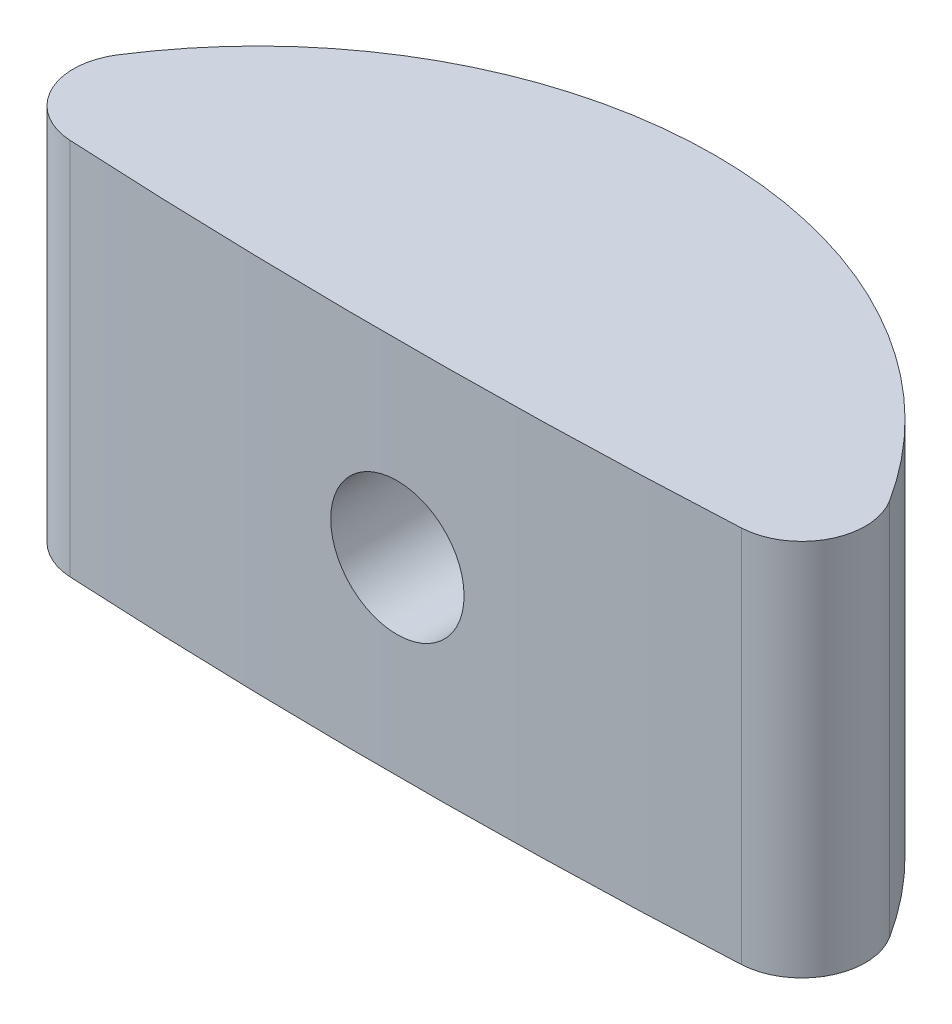
SolidWorks part; units mm, degrees
ref_plane "Front Plane" through (0, 0, 0) normal (0, 0, 1) x (1, 0, 0)
ref_plane "Top Plane" through (0, 0, 0) normal (0, 1, 0) x (1, 0, 0)
ref_plane "Right Plane" through (0, 0, 0) normal (1, 0, 0) x (0, 0, -1)
sketch "Sketch1" plane through (0, 0, 0) normal (0, 1, 0) x (1, 0, 0)
  arc A0 (-4.2854, -1.92) -> (4.2854, -1.92) centre (0, 80.01) ccw
  arc A1 (4.2854, -1.92) -> (4.9281, -0.6727) centre (4.243, -1.1089) ccw
  arc A2 (4.9281, -0.6727) -> (-4.9281, -0.6727) centre (0, -3.81) ccw
  arc A3 (-4.9281, -0.6727) -> (-4.2854, -1.92) centre (-4.243, -1.1089) ccw
  point P8 (0, -2.032)
extrude "Boss-Extrude1" add sketch "Sketch1" along normal blind 4.826
sketch "Sketch2" plane through (0, 0, 0) normal (0, 0, 1) x (1, 0, 0)
  line L0 (0, 4.826) -> (0, 0) construction
  line L1 (4.2854, 4.826) -> (-4.2854, 4.826) construction
  circle A0 centre (0, 2.413) radius 0.8509
  dimension "D1" = 1.7018
extrude "Cut-Extrude1" cut sketch "Sketch2" against normal blind 4.826 and the other way blind 4.826
